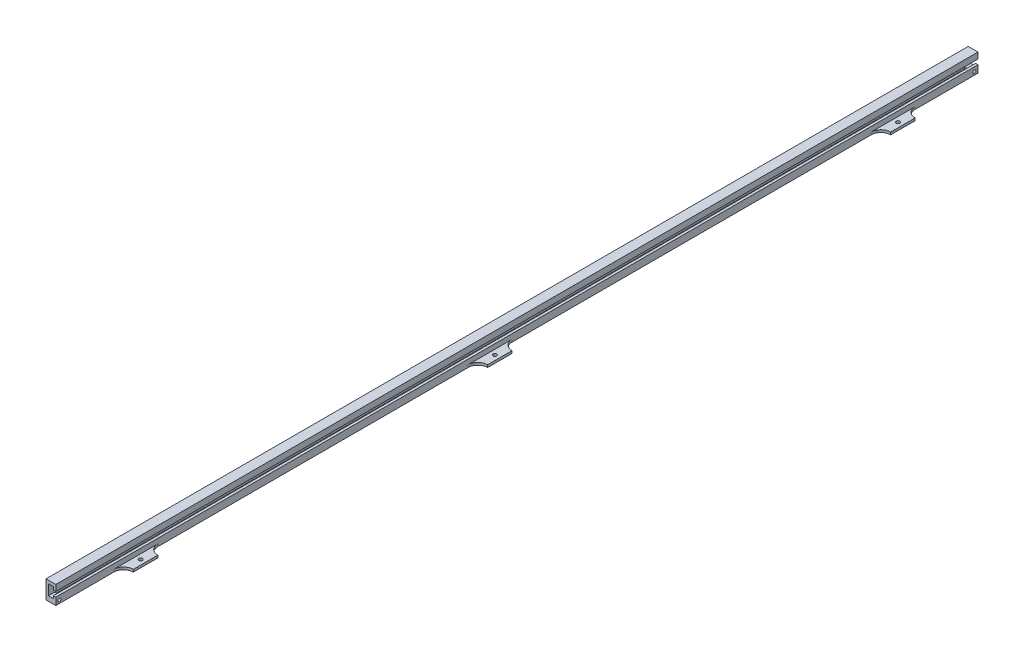
SolidWorks part; units mm, degrees
ref_plane "前视基准面" through (0, 0, 0) normal (0, 0, 1) x (1, 0, 0)
ref_plane "上视基准面" through (0, 0, 0) normal (0, 1, 0) x (1, 0, 0)
ref_plane "右视基准面" through (0, 0, 0) normal (1, 0, 0) x (0, 0, -1)
sketch "草图1" plane through (0, 0, 0) normal (0, 0, 1) x (1, 0, 0)
  line L0 (0.2953, 2.2404) -> (8.2953, 2.2404)
  line L1 (0.2953, 2.2404) -> (0.2953, 17.2404)
  line L2 (0.2953, 17.2404) -> (8.2953, 17.2404)
  line L3 (8.2953, 17.2404) -> (8.2953, 14.7404)
  line L4 (6.2953, 14.7404) -> (2.2953, 14.7404)
  line L5 (2.2953, 14.7404) -> (2.2953, 4.7404)
  line L6 (8.2953, 2.2404) -> (8.2953, 8.2404)
  line L7 (8.2953, 8.2404) -> (6.2953, 8.2404)
  line L8 (8.2953, 14.7404) -> (8.2953, 12.2404)
  line L9 (8.2953, 12.2404) -> (6.2953, 12.2404)
  line L10 (6.2953, 12.2404) -> (6.2953, 14.7404)
  line L11 (6.2953, 8.2404) -> (6.2953, 4.7404)
  line L12 (6.2953, 4.7404) -> (2.2953, 4.7404)
extrude "凸台-拉伸1" add sketch "草图1" along normal blind 755
ref_plane "基准面1" through (0, 2.2404, 0) normal (0, -1, 0) x (-1, 0, 0)
sketch "草图4" plane through (0, 2.2404, 0) normal (0, -1, 0) x (-1, 0, 0)
  line L0 (-8.2953, -679.5) -> (-8.2953, -699.5)
  line L1 (-8.2953, -409.5) -> (-16.2953, -409.5)
  line L2 (-16.2953, -409.5) -> (-16.2953, -389.5)
  line L3 (-16.2953, -389.5) -> (-8.2953, -389.5)
  line L6 (-8.2953, -389.5) -> (-8.2953, -409.5)
  line L7 (-8.2953, -699.5) -> (-16.2953, -699.5)
  line L8 (-16.2953, -699.5) -> (-16.2953, -679.5)
  line L9 (-16.2953, -679.5) -> (-8.2953, -679.5)
  line L10 (-8.2953, -59.5) -> (-8.2953, -79.5)
  line L11 (-8.2953, -79.5) -> (-16.2953, -79.5)
  line L12 (-16.2953, -79.5) -> (-16.2953, -59.5)
  line L13 (-16.2953, -59.5) -> (-8.2953, -59.5)
  circle A0 centre (-12.2953, -69.5) radius 1.5
  circle A1 centre (-12.2953, -399.5) radius 1.5
  circle A2 centre (-12.2953, -689.5) radius 1.5
extrude "凸台-拉伸2" add sketch "草图4" against normal blind 2
sketch "草图5" plane through (0, 0, 755) normal (0, 0, 1) x (1, 0, 0)
  line L0 (6.2953, 4.7404) -> (6.2953, 6.2404)
  line L1 (6.2953, 6.2404) -> (2.2953, 6.2404)
  line L2 (2.2953, 6.2404) -> (2.2953, 4.7404)
  line L12 (0.2953, 17.2404) -> (0.2953, 2.2404)
  line L13 (0.2953, 2.2404) -> (8.2953, 2.2404)
  line L14 (8.2953, 2.2404) -> (8.2953, 8.2404)
  line L15 (8.2953, 8.2404) -> (6.2953, 8.2404)
  line L16 (6.2953, 8.2404) -> (6.2953, 4.7404)
  line L17 (6.2953, 4.7404) -> (2.2953, 4.7404)
  line L18 (2.2953, 4.7404) -> (2.2953, 14.7404)
  line L19 (2.2953, 14.7404) -> (6.2953, 14.7404)
  line L20 (6.2953, 14.7404) -> (6.2953, 12.2404)
  line L21 (6.2953, 12.2404) -> (8.2953, 12.2404)
  line L22 (8.2953, 12.2404) -> (8.2953, 17.2404)
  line L23 (8.2953, 17.2404) -> (0.2953, 17.2404)
  line L24 (0.2953, 17.2404) -> (0.2953, 2.2404)
  line L25 (0.2953, 2.2404) -> (8.2953, 2.2404)
  line L26 (8.2953, 2.2404) -> (8.2953, 8.2404)
  line L27 (8.2953, 8.2404) -> (6.2953, 8.2404)
  line L28 (6.2953, 8.2404) -> (6.2953, 4.7404)
  line L29 (6.2953, 4.7404) -> (2.2953, 4.7404)
  line L30 (2.2953, 4.7404) -> (2.2953, 14.7404)
  line L31 (2.2953, 14.7404) -> (6.2953, 14.7404)
  line L32 (6.2953, 14.7404) -> (6.2953, 12.2404)
  line L33 (6.2953, 12.2404) -> (8.2953, 12.2404)
  line L34 (8.2953, 12.2404) -> (8.2953, 17.2404)
  line L35 (8.2953, 17.2404) -> (0.2953, 17.2404)
  line M17 (6.2953, 8.2404) -> (6.2953, 4.7404)
  line M18 (6.2953, 4.7404) -> (2.2953, 4.7404)
  line M19 (2.2953, 4.7404) -> (2.2953, 14.7404)
  dimension "D1" = 0
fillet "圆角1" radius 8 6 edges at (8.2953, 3.2404, 79.5) (8.2953, 3.2404, 59.5) (8.2953, 3.2404, 389.5) (8.2953, 3.2404, 409.5) (8.2953, 3.2404, 679.5) (8.2953, 3.2404, 699.5)
sketch "草图6" plane through (0, 0, 0) normal (1, 0, 0) x (0, 0, -1)
  line L0 (-755, 8.2404) -> (-752, 8.2404) construction
  line L1 (-752, 8.2404) -> (-752, 4.7404) construction
extrude "凸台-拉伸3" add sketch "草图5" against normal blind 5 contours L1 M17 M19 M18 region at (4.2953, 5.4904, 755)
hole_wizard "M3 螺纹孔2" positions "草图12" profile "草图13" tap size "M3" standard "GB" end condition through all
sketch "草图12" plane through (8.2953, 0, 0) normal (1, 0, 0) x (0, 0, -1)
  point P0 (-752, 4.7404)
sketch "草图13" plane through (8.2953, 4.7404, 752) normal (0, 1, 0) x (0, 0, -1)
  line L0 (0, 0) -> (0, 8)
  line L1 (0, 8) -> (1.25, 8)
  line L2 (1.25, 8) -> (1.25, 0)
  line L5 (1.25, 0) -> (0, 0)
  line L11 (0, -6.35) -> (0, 107.95) construction
  dimension "通孔螺纹孔钻头直径" = 2.5
  dimension "通孔螺纹孔钻头深度" = 8
cosmetic thread "孔螺蚊线3" parameters "D1"=8, "D2"=3
ref_plane "基准面2" through (0, 0, 377.5) normal (0, 0, -1) x (-1, 0, 0)
mirror "镜向1" about plane through (0, 0, 377.5) normal (0, 0, -1) of "M3 螺纹孔2", "凸台-拉伸3"
